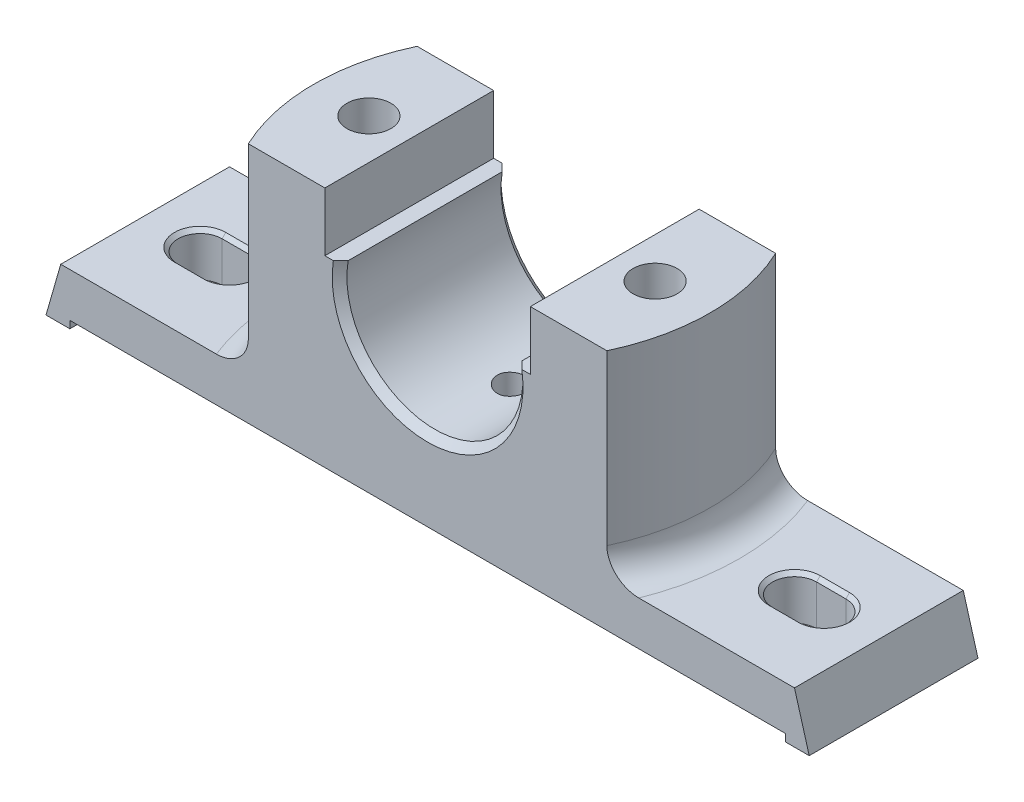
SolidWorks part; units mm, degrees
ref_plane "Front Plane" through (0, 0, 0) normal (0, 0, 1) x (1, 0, 0)
ref_plane "Top Plane" through (0, 0, 0) normal (0, 1, 0) x (1, 0, 0)
ref_plane "Right Plane" through (0, 0, 0) normal (1, 0, 0) x (0, 0, -1)
sketch "Sketch1" plane through (0, 0, 0) normal (0, 0, 1) x (1, 0, 0)
  line L0 (-104, -48) -> (104, -48)
  line L1 (104, -48) -> (99.9856, -34)
  line L2 (99.9856, -34) -> (54, -34)
  line L3 (54, -34) -> (54, 20)
  line L4 (54, 20) -> (28, 20)
  line L5 (28, 20) -> (28, 4)
  line L6 (28, 4) -> (23.6643, 4)
  line L7 (-23.6643, 4) -> (-28, 4)
  line L8 (-28, 4) -> (-28, 20)
  line L9 (-28, 20) -> (-54, 20)
  line L10 (-54, 20) -> (-54, -34)
  line L11 (-54, -34) -> (-99.9856, -34)
  line L12 (-99.9856, -34) -> (-104, -48)
  arc A0 (23.6643, 4) -> (-23.6643, 4) centre (0, 0) cw
  point P4 (0, 0)
  point P19 (0, -48)
  dimension "D7" = 68
  dimension "D5" = 24
  dimension "D1" = 208
  dimension "D2" = 14
  dimension "D3" = 4
  dimension "D4" = 16
  dimension "D6" = 56
  dimension "D8" = 106
  dimension "D10" = 108
extrude "Boss-Extrude1" add sketch "Sketch1" along normal mid plane 46
sketch "Sketch7" plane through (0, 20, 0) normal (0, 1, 0) x (1, 0, 0)
  line L0 (-28, -23) -> (-54, -23) construction
  line L1 (54, -23) -> (28, -23) construction
  line L2 (54, -23) -> (54, 23) construction
  line L3 (-54, -23) -> (-54, 23) construction
  line L4 (-54, -23) -> (-54, 23)
  line L5 (54, -23) -> (54, 23)
  line L6 (54, 23) -> (28, 23) construction
  line L7 (-28, 23) -> (-54, 23) construction
  line L8 (-48.8569, -23) -> (-54, -23)
  line L9 (54, -23) -> (48.8569, -23)
  line L10 (54, 23) -> (48.8569, 23)
  line L11 (-48.8569, 23) -> (-54, 23)
  arc A2 (-48.8569, 23) -> (-48.8569, -23) centre (0, 0) ccw
  arc A3 (48.8569, -23) -> (48.8569, 23) centre (0, 0) ccw
  line M1 (54, 23) -> (28, 23)
  line M3 (28, -23) -> (54, -23)
  line M4 (54, -23) -> (54, 23)
  dimension "D1" = 108
extrude "Cut-Extrude5" cut sketch "Sketch7" against normal up to surface (54 mm away) contours A2 L11 L4 | A2 L4 L8 | A3 L5 M1 | A3 M3 M4 region at (-52.4705, 20, -17.3062) region at (-52.4705, 20, 17.3062) region at (52.4705, 20, 17.3062) region at (52.4705, 20, -17.3062) up to face at (76.9928, -34, 0)
fillet "Fillet1" radius 8 2 edges at (-54, -34, 0) (54, -34, 0)
chamfer "Chamfer1" distance 2 angle 45 2 edges at (0, -24, -23) (0, -24, 23)
sketch "Sketch4" plane through (0, 0, 0) normal (0, 0, 1) x (1, 0, 0)
  line L0 (-97.5, -48) -> (-97.5, -46)
  line L1 (-104, -48) -> (104, -48) construction
  line L2 (-97.5, -46) -> (97.5, -46)
  line L3 (97.5, -46) -> (97.5, -48)
  line L7 (-97.5, -48) -> (97.5, -48)
  point P4 (94.1649, -48)
  point P7 (0, -48)
  point P8 (0, -46)
  dimension "D1" = 2
  dimension "D4" = 195
extrude "Cut-Extrude2" cut sketch "Sketch4" against normal through all both and the other way through all
sketch "Sketch8" plane through (0, -34, 0) normal (0, 1, 0) x (1, 0, 0)
  line L0 (-85, 0) -> (-77, 0) construction
  line L1 (-85, 6) -> (-77, 6)
  line L2 (-85, -6) -> (-77, -6)
  arc A0 (-85, 6) -> (-85, -6) centre (-85, 0) ccw
  arc A1 (-77, -6) -> (-77, 6) centre (-77, 0) ccw
  point P2 (-81, 0)
  dimension "D2" = 6
  dimension "D1" = 8
  dimension "D3" = 77
extrude "Cut-Extrude6" cut sketch "Sketch8" against normal through all
sketch "Sketch5" plane through (0, -46, 0) normal (0, -1, 0) x (1, 0, 0)
  line L1 (-53, -15) -> (-25, -15)
  line L2 (-53, -15) -> (-53, 15)
  line L3 (-53, 15) -> (-25, 15)
  line L4 (-25, -15) -> (-25, 15)
  line L5 (-53, -15) -> (-25, 15) construction
  line L6 (-53, 15) -> (-25, -15) construction
  circle A0 centre (-39, 0) radius 6
  point P0 (-39, 0)
  dimension "D4" = 12
  dimension "D1" = 28
  dimension "D2" = 30
  dimension "D3" = 39
extrude "Cut-Extrude3" cut sketch "Sketch5" against normal blind 10
extrude "Cut-Extrude7" cut sketch "Sketch5<2>" against normal through all contours A0 region at (-39, -46, 0)
sketch "Sketch5<2>" plane through (0, -46, 0) normal (0, -1, 0) x (1, 0, 0) same geometry as "Sketch5"
mirror "Mirror5" about plane through (0, 0, 0) normal (1, 0, 0) of "Cut-Extrude6", "Cut-Extrude3", "Cut-Extrude7"
chamfer "Chamfer2" distance 1 angle 45 8 edges at (-81, -34, 6) (-71, -34, 0) (-91, -34, 0) (-81, -34, -6) (81, -34, -6) (91, -34, 0) (71, -34, 0) (81, -34, 6)
sketch "Sketch9" plane through (0, 0, 0) normal (0, 1, 0) x (1, 0, 0)
  circle A0 centre (0, 0) radius 4
  dimension "D1" = 8
extrude "Cut-Extrude8" cut sketch "Sketch9" against normal blind 36
